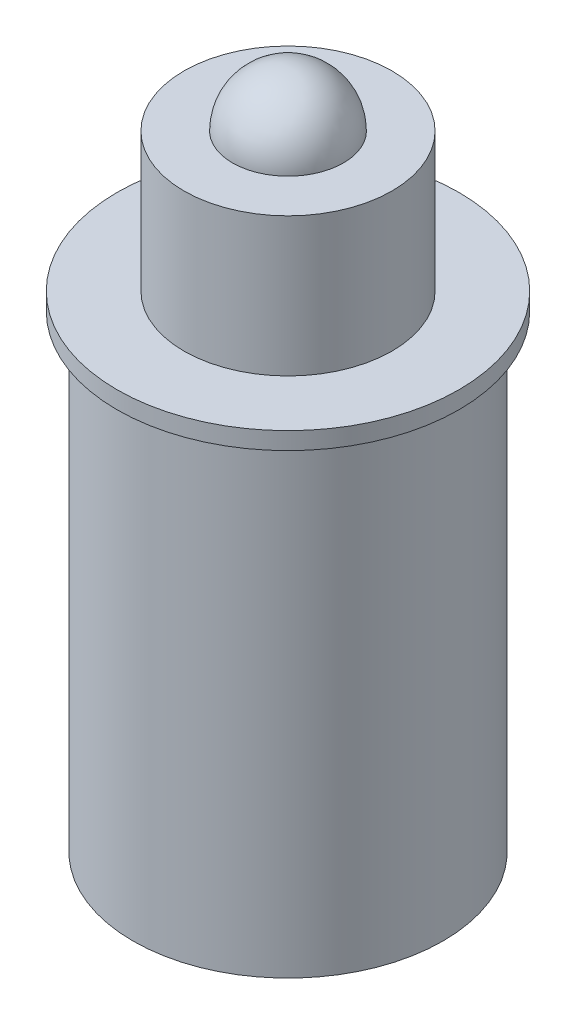
SolidWorks part; units mm, degrees
ref_plane "Front Plane" through (0, 0, 0) normal (0, 0, 1) x (1, 0, 0)
ref_plane "Top Plane" through (0, 0, 0) normal (0, 1, 0) x (1, 0, 0)
ref_plane "Right Plane" through (0, 0, 0) normal (1, 0, 0) x (0, 0, -1)
sketch "Sketch1" plane through (0, 0, 0) normal (0, 1, 0) x (1, 0, 0)
  circle A0 centre (0, 0) radius 2.235
  dimension "D1" = 4.47
extrude "Boss-Extrude1" add sketch "Sketch1" along normal blind 6.75
sketch "Sketch2" plane through (0, 6.75, 0) normal (0, 1, 0) x (1, 0, 0)
  circle A0 centre (0, 0) radius 2.465
  dimension "D1" = 4.93
extrude "Boss-Extrude2" add sketch "Sketch2" along normal blind 0.25
sketch "Sketch4" plane through (0, 7, 0) normal (0, 1, 0) x (1, 0, 0)
  circle A0 centre (0, 0) radius 1.5
  dimension "D1" = 3
extrude "Boss-Extrude3" add sketch "Sketch4" along normal blind 2
sketch "Sketch5" plane through (0, 9, 0) normal (0, 1, 0) x (1, 0, 0)
  circle A0 centre (0, 0) radius 0.8
  dimension "D1" = 1.6
extrude "Boss-Extrude4" add sketch "Sketch5" along normal blind 0.8
fillet "Fillet1" radius 0.8 1 edges at (0, 9.8, 0.8)
